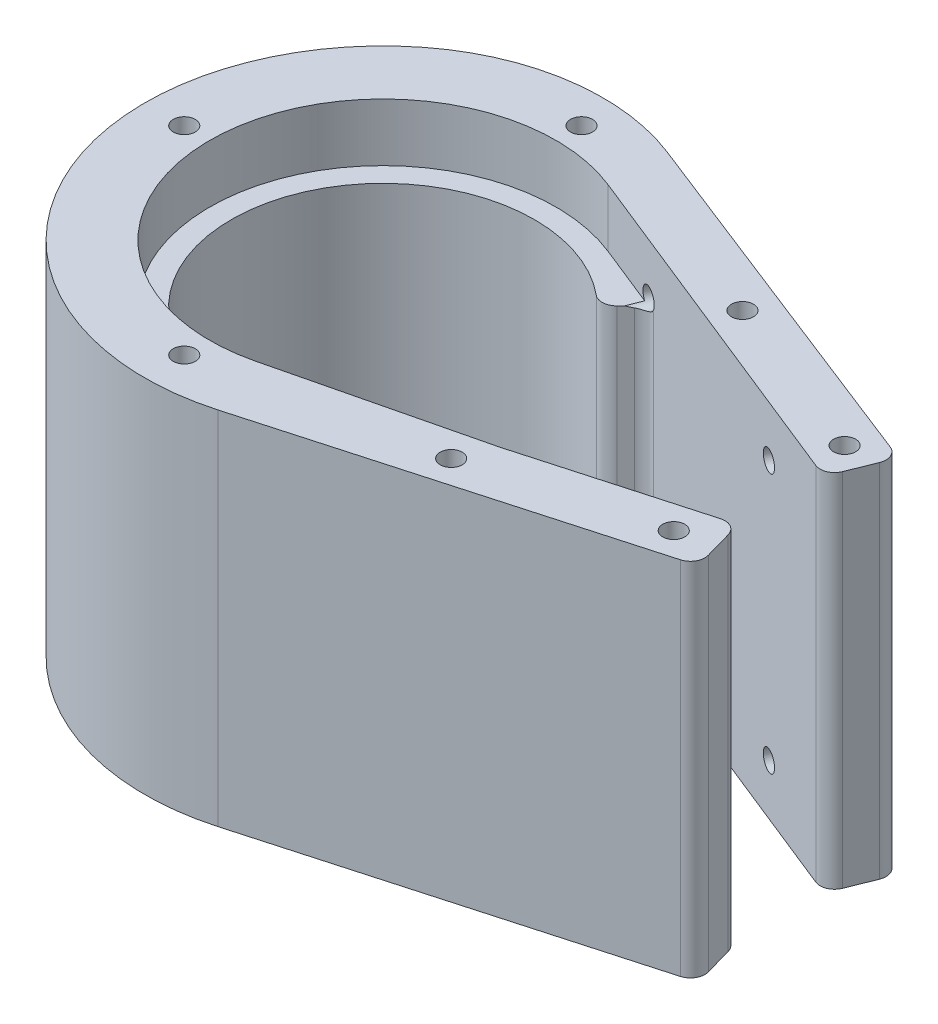
SolidWorks part; units mm, degrees
ref_plane "前视基准面" through (0, 0, 0) normal (0, 0, 1) x (1, 0, 0)
ref_plane "上视基准面" through (0, 0, 0) normal (0, 1, 0) x (1, 0, 0)
ref_plane "右视基准面" through (0, 0, 0) normal (1, 0, 0) x (0, 0, -1)
other "Configuration Table"
sketch "草图1" plane through (0, 0, 0) normal (0, 1, 0) x (1, 0, 0)
  line L0 (0, 0) -> (85, 0) construction
  line L1 (0, 0) -> (78.2429, 33.2121) construction
  line L2 (8.9294, -31.7689) -> (87.7059, -9.627)
  line L3 (-4.1935, 32.7325) -> (76.9721, 43.1311)
  circle A0 centre (0, 0) radius 13.1
  circle A1 centre (0, 0) radius 17.5 construction
  circle A2 centre (0, 17.5) radius 2.025
  circle A3 centre (8.75, 15.1554) radius 2.025
  circle A4 centre (15.1554, 8.75) radius 2.025
  circle A5 centre (17.5, 0) radius 2.025
  circle A6 centre (15.1554, -8.75) radius 2.025
  circle A7 centre (8.75, -15.1554) radius 2.025
  circle A8 centre (0, -17.5) radius 2.025
  circle A9 centre (-8.75, -15.1554) radius 2.025
  circle A10 centre (-15.1554, -8.75) radius 2.025
  circle A11 centre (-17.5, 0) radius 2.025
  circle A12 centre (-15.1554, 8.75) radius 2.025
  circle A13 centre (-8.75, 15.1554) radius 2.025
  circle A14 centre (0, 0) radius 33
  circle A15 centre (85, 0) radius 3
  circle A16 centre (78.2429, 33.2121) radius 3
  circle A17 centre (78.2429, 33.2121) radius 10
  circle A18 centre (85, 0) radius 10
  circle A19 centre (163.2429, 33.2121) radius 75
  point P31 (0, 0)
  dimension "D1" = 26.2
  dimension "D2" = 35
  dimension "D3" = 4.05
  dimension "D5" = 66
  dimension "D6" = 6
  dimension "D9" = 20
  dimension "D10" = 150
  dimension "D7" = 85
  dimension "D8" = 23
  dimension "D4" = 12
extrude "凸台-拉伸1" add sketch "草图1" along normal mid plane 50 contours A19 A17 L3 A14 L2 A18 | A14 A0 A2 A3 A4 A5 A6 A7 A8 A9 A10 A11 A12 A13 | A18 A15 | A17 A16 region at (51.8594, 0, -10.5509) region at (-31.4229, 0, 6.3931) region at (76.2404, 0, -4.2063) region at (84.6626, 0, -40.5067)
sketch "草图3" plane through (0, 25, 0) normal (0, 1, 0) x (1, 0, 0)
  circle A0 centre (0, 0) radius 24
  dimension "D1" = 48
extrude "切除-拉伸2" cut sketch "草图3" against normal blind 10
sketch "草图4" plane through (0, 25, 0) normal (0, 1, 0) x (1, 0, 0)
  line L0 (25.9945, -18.6624) -> (76.1087, -4.5766)
  line L1 (8.9294, -31.7689) -> (87.7059, -9.627) construction
  line L2 (28.7852, 13.979) -> (76.1087, -4.5766)
  line L3 (75.8816, 4.1055) -> (16.6361, 27.3357)
  line L4 (16.6361, 27.3357) -> (69.7704, 34.143)
  line L5 (-4.1935, 32.7325) -> (76.9721, 43.1311) construction
  line L6 (69.7704, 34.143) -> (75.8816, 4.1055)
  line L7 (78.2429, 33.2121) -> (85, 0) construction
  circle A0 centre (0, 0) radius 32
  circle A1 centre (85, 0) radius 10
  dimension "D1" = 64
  dimension "D2" = 20
  dimension "D3" = 8
  dimension "D4" = 8
  dimension "D5" = 8
extrude "切除-拉伸3" cut sketch "草图4" against normal blind 10 contours L6 L4 L3 | A0 L0 L2 region at (45.6958, 25, 3.1712) region at (54.096, 25, -21.8614)
fillet "圆角1" radius 3 6 edges at (28.7852, 20, -13.979) (76.1087, 20, 4.5766) (25.9945, 20, 18.6624) (16.6361, 20, -27.3357) (69.7704, 20, -34.143) (75.8816, 20, -4.1055)
sketch "草图7" plane through (0, -25, 0) normal (0, -1, 0) x (1, 0, 0)
  circle A0 centre (0, -27.5222) radius 1.525 construction
  circle A1 centre (33.3215, -16.4968) radius 1.525 construction
  circle A2 centre (-27.5222, 0) radius 1.525 construction
  circle A3 centre (0, 27.5222) radius 1.525 construction
  circle A4 centre (30.9017, 21.4381) radius 1.525 construction
  circle A5 centre (56.5963, -7.3707) radius 1.525 construction
  circle A6 centre (54.9691, 14.6734) radius 1.525 construction
  circle A7 centre (0, -27.5222) radius 1.525
  circle A8 centre (33.3215, -16.4968) radius 1.525
  circle A9 centre (-27.5222, 0) radius 1.525
  circle A10 centre (0, 27.5222) radius 1.525
  circle A11 centre (30.9017, 21.4381) radius 1.525
  circle A12 centre (56.5963, -7.3707) radius 1.525
  circle A13 centre (54.9691, 14.6734) radius 1.525
extrude "切除-拉伸4" cut sketch "草图7" against normal blind 50
sketch "草图8" plane through (0, 25, 0) normal (0, 1, 0) x (1, 0, 0)
  line L0 (94.4787, -3.1865) -> (1.1322, 33.4148)
  line L1 (70.7472, 6.1187) -> (27.5492, 23.0566) construction
  line L2 (-4.1935, 32.7325) -> (76.9721, 43.1311) construction
  line L3 (56.5963, 7.3707) -> (54.9691, -14.6734) construction
  line L4 (64.7007, 8.4895) -> (62.8476, -16.614)
  line L5 (76.9721, 43.1311) -> (-4.1935, 32.7325)
  line L6 (8.9294, -31.7689) -> (87.7059, -9.627)
  line L7 (76.9721, 43.1311) -> (-4.1935, 32.7325)
  line L8 (8.9294, -31.7689) -> (87.7059, -9.627)
  arc A0 (87.7059, -9.627) -> (94.205, 3.9073) centre (85, 0) ccw construction
  arc A5 (88.2429, 33.2121) -> (94.205, 3.9073) centre (163.2429, 33.2121) ccw
  arc A6 (88.2429, 33.2121) -> (76.9721, 43.1311) centre (78.2429, 33.2121) ccw
  arc A7 (-4.1935, 32.7325) -> (8.9294, -31.7689) centre (0, 0) ccw
  arc A8 (87.7059, -9.627) -> (94.205, 3.9073) centre (85, 0) ccw
  arc A9 (88.2429, 33.2121) -> (94.205, 3.9073) centre (163.2429, 33.2121) ccw
  arc A10 (88.2429, 33.2121) -> (76.9721, 43.1311) centre (78.2429, 33.2121) ccw
  arc A11 (-4.1935, 32.7325) -> (8.9294, -31.7689) centre (0, 0) ccw
  arc A12 (87.7059, -9.627) -> (94.205, 3.9073) centre (85, 0) ccw
  arc M16 (94.205, 3.9073) -> (88.2429, 33.2121) centre (163.2429, 33.2121) cw
  arc M17 (88.2429, 33.2121) -> (76.9721, 43.1311) centre (78.2429, 33.2121) ccw
  line M18 (76.9721, 43.1311) -> (-4.1935, 32.7325)
  line M20 (8.9294, -31.7689) -> (87.7059, -9.627)
  arc M21 (87.7059, -9.627) -> (94.205, 3.9073) centre (85, 0) ccw
  circle M22 centre (85, 0) radius 3
  circle M23 centre (78.2429, 33.2121) radius 3
  line M24 (70.7472, 6.1187) -> (27.5492, 23.0566)
  arc M25 (27.5492, 23.0566) -> (28.2631, 28.8253) centre (28.6444, 25.8496) cw
  line M26 (28.2631, 28.8253) -> (67.0052, 33.7888)
  arc M27 (67.0052, 33.7888) -> (70.3262, 31.4112) centre (67.3864, 30.8131) cw
  line M28 (70.3262, 31.4112) -> (74.7821, 9.5097)
  arc M29 (74.7821, 9.5097) -> (70.7472, 6.1187) centre (71.8423, 8.9116) cw
  line M30 (67.5045, -6.995) -> (32.9705, -16.7016)
  line M34 (34.9821, 11.5492) -> (67.7878, -1.314)
  arc M35 (67.7878, -1.314) -> (67.5045, -6.995) centre (66.6927, -4.1069) cw
  dimension "D2" = 8
  dimension "D1" = 0
extrude "切除-拉伸5" cut sketch "草图8" against normal blind 50 contours L0 M24 M29 M28 M27 M26 M25 | L0 M21 M16 M17 M18 M25 M26 M27 M28 M29 M22 M23 | L4 L0 M24 M34 M35 M30 M20 M21 M22 region at (75.6586, 25, 4.7768) region at (74.4462, 25, -5.8134) region at (54.8083, 25, -21.8381)
sketch "草图9" plane through (0, 25, 0) normal (0, 1, 0) x (1, 0, 0)
  line L0 (32.9705, -16.7016) -> (5.655, -23.3243)
  line L1 (64.0842, 0.1382) -> (8.9401, 22.2727)
  line L2 (34.9821, 11.5492) -> (64.0842, 0.1382) construction
  line L10 (64.7007, 8.4895) -> (1.1322, 33.4148)
  line L11 (1.1322, 33.4148) -> (-4.1935, 32.7325)
  line L12 (8.9294, -31.7689) -> (62.8476, -16.614)
  line L13 (62.8476, -16.614) -> (63.474, -8.1279)
  line L14 (63.474, -8.1279) -> (32.9705, -16.7016)
  line L15 (34.9821, 11.5492) -> (64.0842, 0.1382)
  line L16 (64.0842, 0.1382) -> (64.7007, 8.4895)
  line L17 (64.7007, 8.4895) -> (1.1322, 33.4148)
  line L18 (1.1322, 33.4148) -> (-4.1935, 32.7325)
  line L19 (8.9294, -31.7689) -> (62.8476, -16.614)
  line L20 (62.8476, -16.614) -> (63.474, -8.1279)
  line L21 (63.474, -8.1279) -> (32.9705, -16.7016)
  line L22 (34.9821, 11.5492) -> (64.0842, 0.1382)
  line L23 (64.0842, 0.1382) -> (64.7007, 8.4895)
  circle A0 centre (0, 0) radius 24 construction
  circle A1 centre (0, 0) radius 24
  arc A5 (-4.1935, 32.7325) -> (8.9294, -31.7689) centre (0, 0) ccw
  arc A6 (29.4023, -12.6295) -> (32.9705, -16.7016) centre (32.1588, -13.8135) ccw
  arc A7 (29.4023, -12.6295) -> (30.9824, 8.0057) centre (0, 0) ccw
  arc A8 (34.9821, 11.5492) -> (30.9824, 8.0057) centre (33.887, 8.7562) ccw
  arc A9 (-4.1935, 32.7325) -> (8.9294, -31.7689) centre (0, 0) ccw
  arc A10 (29.4023, -12.6295) -> (32.9705, -16.7016) centre (32.1588, -13.8135) ccw
  arc A11 (29.4023, -12.6295) -> (30.9824, 8.0057) centre (0, 0) ccw
  arc A12 (34.9821, 11.5492) -> (30.9824, 8.0057) centre (33.887, 8.7562) ccw
  circle M14 centre (0, 0) radius 24
  arc M28 (32.9705, -16.7016) -> (29.4023, -12.6295) centre (32.1588, -13.8135) cw
  arc M29 (29.4023, -12.6295) -> (30.9824, 8.0057) centre (0, 0) ccw
  arc M30 (30.9824, 8.0057) -> (34.9821, 11.5492) centre (33.887, 8.7562) cw
  line M31 (34.9821, 11.5492) -> (64.0842, 0.1382)
  dimension "D1" = 0
extrude "切除-拉伸6" cut sketch "草图9" against normal blind 10 contours L1 L0 M31 M14 M28 M29 M30 region at (25.4218, 25, 1.6522)
fillet "圆角2" radius 30 1 edges at (1.1322, 0, -33.4148)
sketch "草图10" plane through (0, 15, 0) normal (0, 1, 0) x (1, 0, 0)
  line L10 (5.655, -23.3243) -> (32.7598, -16.7527)
  line L11 (32.9705, -16.7016) -> (63.474, -8.1279)
  line L12 (63.474, -8.1279) -> (67.5045, -6.995)
  line L13 (67.7878, -1.314) -> (64.0842, 0.1382)
  line L14 (64.0842, 0.1382) -> (8.9401, 22.2727)
  line L15 (5.655, -23.3243) -> (32.7598, -16.7527)
  line L16 (32.9705, -16.7016) -> (63.474, -8.1279)
  line L17 (63.474, -8.1279) -> (67.5045, -6.995)
  line L18 (67.7878, -1.314) -> (64.0842, 0.1382)
  line L19 (64.0842, 0.1382) -> (8.9401, 22.2727)
  arc A6 (8.9401, 22.2727) -> (5.655, -23.3243) centre (0, 0) ccw
  arc A7 (32.7598, -16.7527) -> (32.9705, -16.7016) centre (32.1588, -13.8135) ccw
  arc A8 (67.5045, -6.995) -> (67.7878, -1.314) centre (66.6927, -4.1069) ccw
  arc A9 (8.9401, 22.2727) -> (5.655, -23.3243) centre (0, 0) ccw
  arc A10 (32.7598, -16.7527) -> (32.9705, -16.7016) centre (32.1588, -13.8135) ccw
  arc A11 (67.5045, -6.995) -> (67.7878, -1.314) centre (66.6927, -4.1069) ccw
  dimension "D1" = 0
extrude "切除-拉伸7" cut sketch "草图10" against normal blind 100
sketch "草图11" plane through (0, 25, 0) normal (0, 1, 0) x (1, 0, 0)
  line L0 (61.8105, 9.6228) -> (58.8472, 2.2403)
  line L1 (64.7007, 8.4895) -> (9.1002, 30.2905) construction
  line L2 (64.0842, 0.1382) -> (8.9401, 22.2727) construction
  line L3 (58.7002, -9.4697) -> (60.8649, -17.1712)
  line L4 (32.9705, -16.7016) -> (63.474, -8.1279) construction
  line L5 (8.9294, -31.7689) -> (62.8476, -16.614) construction
  line L22 (64.7007, 8.4895) -> (9.1002, 30.2905)
  line L24 (8.9294, -31.7689) -> (62.8476, -16.614)
  line L25 (62.8476, -16.614) -> (63.474, -8.1279)
  line L26 (63.474, -8.1279) -> (32.9705, -16.7016)
  line L27 (32.7598, -16.7527) -> (5.655, -23.3243)
  line L28 (8.9401, 22.2727) -> (64.0842, 0.1382)
  line L29 (64.0842, 0.1382) -> (64.7007, 8.4895)
  line L30 (64.7007, 8.4895) -> (9.1002, 30.2905)
  line L32 (8.9294, -31.7689) -> (62.8476, -16.614)
  line L33 (62.8476, -16.614) -> (63.474, -8.1279)
  line L34 (63.474, -8.1279) -> (32.9705, -16.7016)
  line L35 (32.7598, -16.7527) -> (5.655, -23.3243)
  line L36 (8.9401, 22.2727) -> (64.0842, 0.1382)
  line L37 (64.0842, 0.1382) -> (64.7007, 8.4895)
  circle A0 centre (56.5963, 7.3707) radius 1.525 construction
  circle A1 centre (54.9691, -14.6734) radius 1.525 construction
  arc A10 (9.1002, 30.2905) -> (-20.3621, 25.9689) centre (-1.8511, 2.3608) ccw
  arc A11 (-20.3621, 25.9689) -> (8.9294, -31.7689) centre (0, 0) ccw
  arc A12 (32.7598, -16.7527) -> (32.9705, -16.7016) centre (32.1588, -13.8135) ccw
  arc A13 (8.9401, 22.2727) -> (5.655, -23.3243) centre (0, 0) ccw
  arc A14 (9.1002, 30.2905) -> (-20.3621, 25.9689) centre (-1.8511, 2.3608) ccw
  arc A15 (-20.3621, 25.9689) -> (8.9294, -31.7689) centre (0, 0) ccw
  arc A16 (32.7598, -16.7527) -> (32.9705, -16.7016) centre (32.1588, -13.8135) ccw
  arc A17 (8.9401, 22.2727) -> (5.655, -23.3243) centre (0, 0) ccw
  line M22 (64.7007, 8.4895) -> (9.1002, 30.2905)
  line M26 (8.9294, -31.7689) -> (62.8476, -16.614)
  line M27 (62.8476, -16.614) -> (63.474, -8.1279)
  line M28 (63.474, -8.1279) -> (32.9705, -16.7016)
  line M32 (8.9401, 22.2727) -> (64.0842, 0.1382)
  line M33 (64.0842, 0.1382) -> (64.7007, 8.4895)
  dimension "D1" = 4
  dimension "D2" = 5
  dimension "D3" = 0
extrude "切除-拉伸8" cut sketch "草图11" against normal blind 100 contours L0 M22 M32 M33 | L3 M28 M26 M27 region at (62.2756, 25, -4.7424) region at (61.4187, 25, 12.2884)
sketch "草图12" plane through (0, 25, 0) normal (0, 1, 0) x (1, 0, 0)
  line L0 (18.2204, 18.5477) -> (0, 0)
  line L1 (8.9401, 22.2727) -> (18.2204, 18.5477)
  line L2 (58.8472, 2.2403) -> (8.9401, 22.2727) construction
  line L3 (0, 0) -> (15.3734, -20.968)
  line L4 (5.655, -23.3243) -> (15.3734, -20.968)
  line L5 (32.7598, -16.7527) -> (5.655, -23.3243) construction
  line L7 (56.5963, 7.3707) -> (54.9691, -14.6734) construction
  circle A0 centre (0, 0) radius 21
  arc A1 (8.9401, 22.2727) -> (5.655, -23.3243) centre (0, 0) ccw construction
  arc A2 (8.9401, 22.2727) -> (5.655, -23.3243) centre (0, 0) ccw
  line M16 (32.7598, -16.7527) -> (5.655, -23.3243)
  arc M17 (5.655, -23.3243) -> (8.9401, 22.2727) centre (0, 0) cw
  line M18 (8.9401, 22.2727) -> (58.8472, 2.2403)
  dimension "D1" = 42
  dimension "D2" = 10
extrude "凸台-拉伸2" add sketch "草图12" against normal up to surface (50 mm away) contours A0 L0 L3 M18 M17 M16 region at (16.0124, 25, -17.2122) up to face at (23.8812, -25, 2.7874)
sketch "草图13" plane through (0, 25, 0) normal (0, 1, 0) x (1, 0, 0)
  line L0 (26.1128, 15.3797) -> (20.2574, 17.7301) construction
  line L2 (58.8472, 2.2403) -> (18.2204, 18.5477) construction
  line L3 (18.2204, 18.5477) -> (8.9401, 22.2727)
  line L4 (15.3734, -20.968) -> (5.655, -23.3243)
  line L5 (18.2204, 18.5477) -> (14.7165, 14.9808)
  line L6 (15.3734, -20.968) -> (12.417, -16.9357)
  circle A0 centre (0, 0) radius 21
  circle A1 centre (0, 0) radius 24
  arc A2 (14.7165, 14.9808) -> (12.417, -16.9357) centre (0, 0) ccw construction
  line M10 (15.3734, -20.968) -> (12.417, -16.9357)
  arc M11 (12.417, -16.9357) -> (14.7165, 14.9808) centre (0, 0) cw
  line M12 (14.7165, 14.9808) -> (18.2204, 18.5477)
extrude "切除-拉伸9" cut sketch "草图13" against normal blind 8 contours A1 L5 L3 | A1 L6 M11 M12 | A1 L4 M10 region at (15.4404, 25, -19.0629) region at (12.7897, 25, -19.5595) region at (12.5483, 25, 21.0795)
mirror "镜向1" about plane through (0, 0, 0) normal (0, 1, 0) of "切除-拉伸9"
fillet "圆角3" radius 2 4 edges at (15.3734, 0, 20.968) (12.417, 0, 16.9357) (18.2204, 0, -18.5477) (14.7165, 0, -14.9808)
fillet "圆角4" radius 2 5 edges at (61.8105, 0, -9.6228) (58.7002, 0, 9.4697) (32.7598, 0, 16.7527) (60.8649, 0, 17.1712) (58.8472, 0, -2.2403)
sketch "草图15" plane through (11.5069, 0, -29.3468) normal (0.365, 0, -0.931) x (-0.931, 0, -0.365)
  line L0 (0, 0) -> (50000, 0) construction
  line L1 (-10.2738, -18) -> (-40.2738, -18) construction
  line L2 (-10.2738, -18) -> (-10.2738, 18) construction
  line L3 (-10.2738, 18) -> (-40.2738, 18) construction
  line L4 (-40.2738, -18) -> (-40.2738, 18) construction
  line L5 (-10.2738, -18) -> (-40.2738, 18) construction
  line L6 (-10.2738, 18) -> (-40.2738, -18) construction
  circle A0 centre (-40.2738, -18) radius 1.4
  circle A1 centre (-40.2738, 18) radius 1.4
  circle A2 centre (-10.2738, 18) radius 1.4
  circle A3 centre (-10.2738, -18) radius 1.4
  point P0 (-25.2738, 0)
  dimension "D1" = 2.8
  dimension "D2" = 36
  dimension "D3" = 30
extrude "切除-拉伸10" cut sketch "草图15" against normal blind 10
